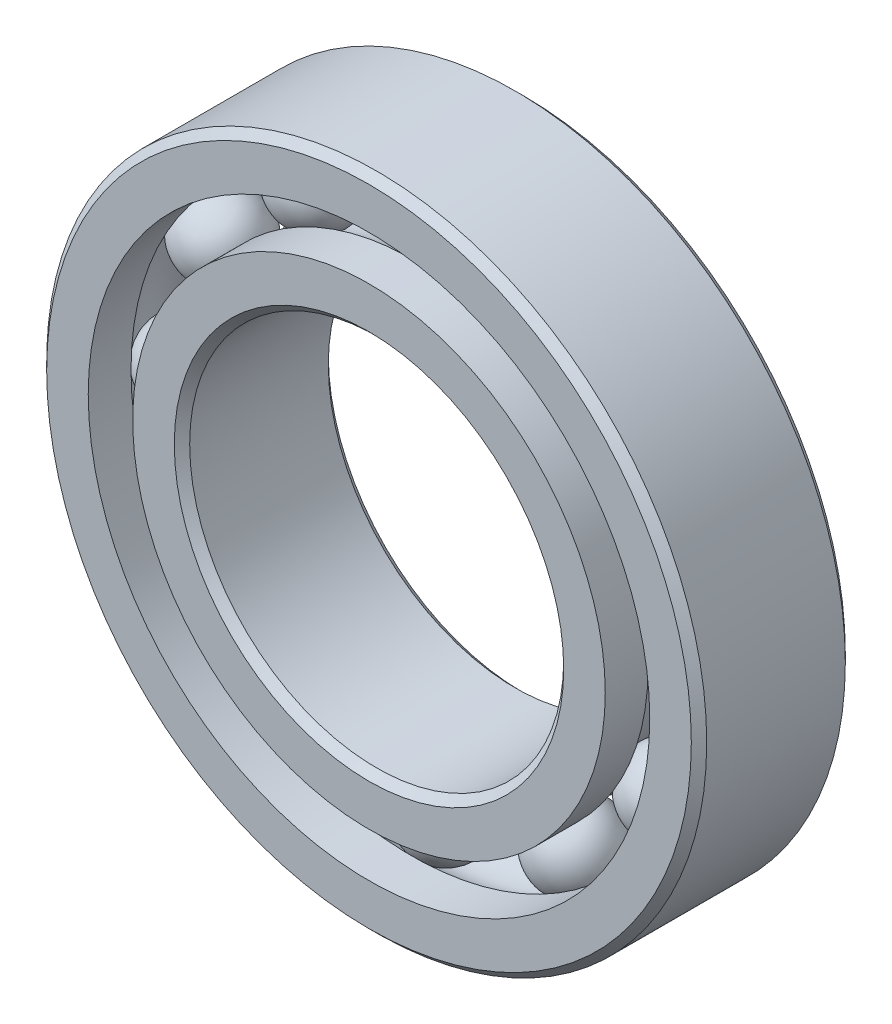
SolidWorks part; units mm, degrees
ref_plane "Front Plane" through (0, 0, 0) normal (0, 0, 1) x (1, 0, 0)
ref_plane "Top Plane" through (0, 0, 0) normal (0, 1, 0) x (1, 0, 0)
ref_plane "Right Plane" through (0, 0, 0) normal (1, 0, 0) x (0, 0, -1)
sketch "Sketch1" plane through (0, 0, 0) normal (1, 0, 0) x (0, 0, -1)
  line L0 (-3.5, 0) -> (3.5, 0) construction
  line L1 (0, 15) -> (0, -15) construction
  line L2 (3.15, 15) -> (-3.15, 15)
  line L3 (-3.15, 15) -> (-3.5, 14.65)
  line L4 (-3.5, 14.65) -> (-3.5, 12.761)
  line L5 (-3.5, 12.761) -> (-1.5556, 12.761)
  line L6 (3.5, 12.761) -> (1.5556, 12.761)
  line L7 (3.5, 14.65) -> (3.5, 12.761)
  line L8 (3.15, 15) -> (3.5, 14.65)
  line L9 (0, 15) -> (0, 11.75) construction
  line L10 (0, 11.75) -> (0, 8.5) construction
  arc A0 (-1.5556, 12.761) -> (1.5556, 12.761) centre (0, 11.75) cw
  point P14 (0, 8.5)
  dimension "Width" = 7
  dimension "OD" = 30
  dimension "D1" = 45
  dimension "D2" = 0.35
  dimension "Shaft Dia" = 17
  dimension "D3" = 3.1111
  dimension "D4" = 1.011
revolve "Revolve1" add sketch "Sketch1" angle 360 about L0
sketch "Sketch3" plane through (0, 0, 0) normal (1, 0, 0) x (0, 0, -1)
  line L0 (-3.5, 10.739) -> (-1.5556, 10.739)
  line L1 (0, 15) -> (0, -15) construction
  line L2 (-3.5, 14.65) -> (-3.5, 12.761) construction
  line L3 (-3.5, 10.739) -> (-3.5, 8.85)
  line L4 (-3.15, 15) -> (-3.5, 14.65) construction
  line L5 (-3.5, 8.85) -> (-3.15, 8.5)
  line L6 (-3.15, 8.5) -> (3.15, 8.5)
  line L7 (3.15, 15) -> (3.15, -15) construction
  line L8 (3.15, 8.5) -> (3.5, 8.85)
  line L9 (3.5, -14.65) -> (3.5, 14.65) construction
  line L10 (3.5, 8.85) -> (3.5, 10.739)
  line L11 (3.5, 10.739) -> (1.5556, 10.739)
  line L13 (3.15, 15) -> (3.5, 14.65) construction
  arc A0 (1.5556, 12.761) -> (-1.5556, 12.761) centre (0, 11.75) ccw construction
  arc A1 (1.5556, 10.739) -> (-1.5556, 10.739) centre (0, 11.75) cw
revolve "Revolve3" add sketch "Sketch3" angle 360 about L0
sketch "Sketch4" plane through (0, 0, 0) normal (1, 0, 0) x (0, 0, -1)
  line L0 (-1.8552, 11.75) -> (1.8552, 11.75)
  arc A2 (-1.8552, 11.75) -> (1.8552, 11.75) centre (0, 11.75) cw
  arc A3 (1.5556, 12.761) -> (-1.5556, 12.761) centre (0, 11.75) ccw construction
revolve "Revolve4" add sketch "Sketch4" angle 360 about L0
ref_axis "Axis1" through (0, 0, -3.5) along (0, 0, 1)
pattern_circular "CirPattern1" count 12 every 30 about axis through (0, 0, -3.5) along (0, 0, 1) of bodies 104
sketch "Sketch5" plane through (0, 0, 0) normal (1, 0, 0) x (0, 0, -1)
  line L0 (-3.5, 12.761) -> (-1.5556, 12.761) construction
  line L1 (-3.325, 12.761) -> (-1.8552, 12.761)
  line L2 (-3.325, 12.761) -> (-3.325, 10.739)
  line L3 (-3.325, 10.739) -> (-1.8552, 10.739)
  line L4 (-1.8552, 12.761) -> (-1.8552, 10.739)
  line L5 (-3.5, 10.739) -> (-1.5556, 10.739) construction
  line L6 (3.5, 12.761) -> (1.5556, 12.761) construction
  line L7 (3.325, 12.761) -> (1.8552, 12.761)
  line L8 (3.325, 12.761) -> (3.325, 10.739)
  line L9 (3.325, 10.739) -> (1.8552, 10.739)
  line L10 (1.8552, 12.761) -> (1.8552, 10.739)
  line L11 (3.5, 10.739) -> (1.5556, 10.739) construction
  line L12 (-3.15, 15) -> (-3.5, 14.65) construction
  point P18 (-3.325, 14.825)
equation "\"D2@Sketch1\" = \"Width@Sketch1\"*.05"
equation "\"D3@Sketch1\" = \"Width@Sketch1\"/2.25"
equation "\"D4@Sketch1\" = (((\"OD@Sketch1\"-\"Width@Sketch1\")/2)/3.25)/3.5"
equation "\"D2@CirPattern1\" = 360/\"Balls@CirPattern1\""
